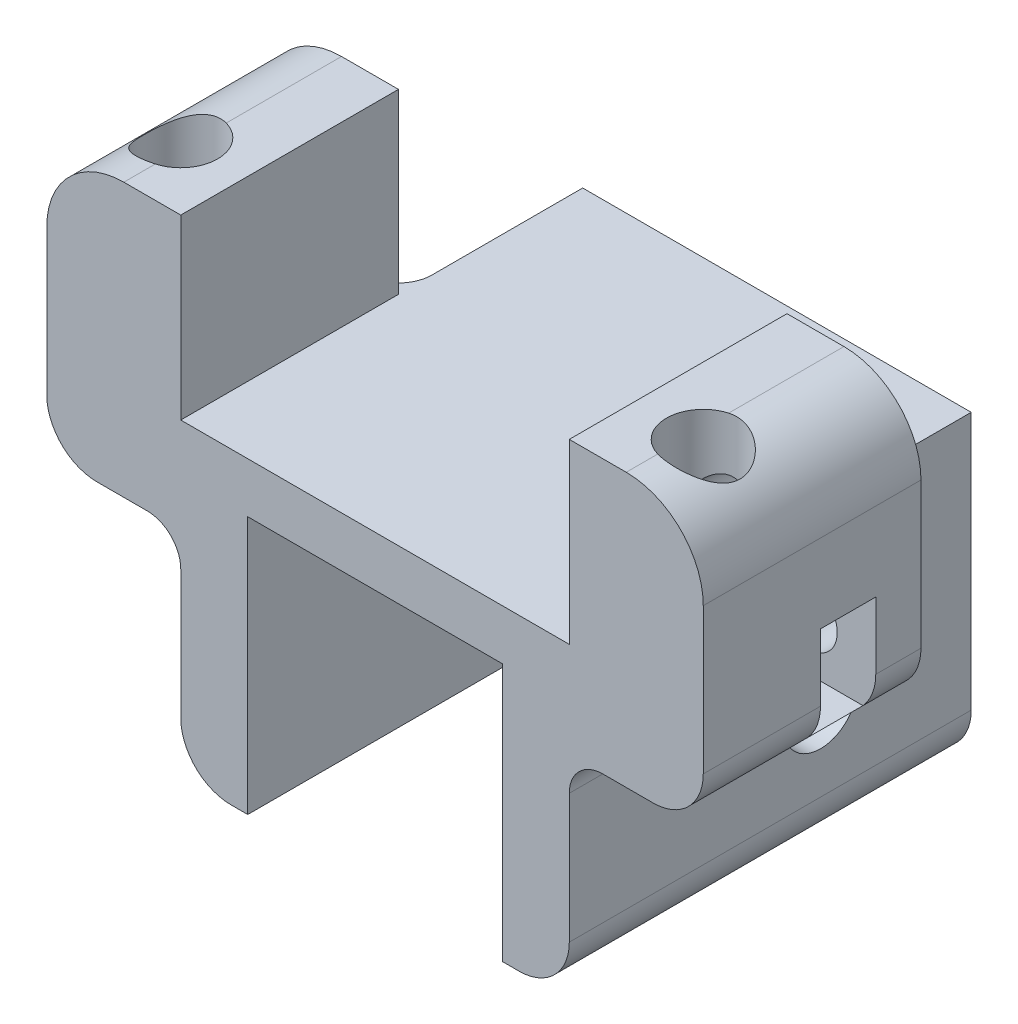
SolidWorks part; units mm, degrees
ref_plane "前视基准面" through (0, 0, 0) normal (0, 0, 1) x (1, 0, 0)
ref_plane "上视基准面" through (0, 0, 0) normal (0, 1, 0) x (1, 0, 0)
ref_plane "右视基准面" through (0, 0, 0) normal (1, 0, 0) x (0, 0, -1)
sketch "草图1" plane through (0, 0, 0) normal (0, 0, 1) x (1, 0, 0)
  line L0 (0, -1000) -> (0, 49000) construction
  line L1 (-7.6, -7.7) -> (7.6, -7.7) construction
  line L2 (-7.6, -7.7) -> (-7.6, 7.7)
  line L3 (-7.6, 7.7) -> (7.6, 7.7)
  line L4 (7.6, -7.7) -> (7.6, 7.7)
  line L5 (-7.6, -7.7) -> (7.6, 7.7) construction
  line L6 (-7.6, 7.7) -> (7.6, -7.7) construction
  line L7 (-11.6, 10.7) -> (11.6, 10.7) construction
  line L8 (-11.6, 10.7) -> (-11.6, 22.7) construction
  line L9 (-11.6, 22.7) -> (11.6, 22.7) construction
  line L10 (11.6, 10.7) -> (11.6, 22.7) construction
  line L11 (-11.6, 10.7) -> (11.6, 22.7) construction
  line L12 (-11.6, 22.7) -> (11.6, 10.7) construction
  line L13 (-7.6, -7.7) -> (-8.6, -7.7)
  line L14 (-11.6, -4.7) -> (-11.6, 3)
  line L15 (13.6, 5) -> (16.6, 5)
  line L16 (-19.6, 8) -> (-19.6, 16.7)
  line L17 (-15, 21.3) -> (-11.6, 21.3)
  line L18 (-11.6, 21.3) -> (-11.6, 10.7)
  line L19 (-11.6, 10.7) -> (11.6, 10.7)
  line L20 (11.6, 21.3) -> (11.6, 10.7)
  line L21 (15, 21.3) -> (11.6, 21.3)
  line L22 (19.6, 8) -> (19.6, 16.7)
  line L23 (-13.6, 5) -> (-16.6, 5)
  line L24 (11.6, -4.7) -> (11.6, 3)
  line L25 (7.6, -7.7) -> (8.6, -7.7)
  line L26 (-11.6, 5) -> (-11.6, 10.7)
  line L27 (11.6, 5) -> (11.6, 10.7)
  line L28 (-1000, 0) -> (49000, 0) construction
  line L29 (17.3321, 12) -> (19.6, 12)
  line L30 (19.0641, 9) -> (17.3321, 12) construction
  line L31 (17.3321, 12) -> (13.8679, 12)
  line L32 (13.8679, 12) -> (12.1359, 9)
  line L33 (12.1359, 9) -> (13.8679, 6)
  line L34 (13.8679, 6) -> (17.3321, 6)
  line L35 (17.3321, 6) -> (19.0641, 9) construction
  line L36 (17.3321, 6) -> (18.8361, 6)
  line L37 (-17.3321, 12) -> (-19.6, 12)
  line L38 (-17.3321, 12) -> (-13.8679, 12)
  line L39 (-13.8679, 12) -> (-12.1359, 9)
  line L40 (-12.1359, 9) -> (-13.8679, 6)
  line L41 (-13.8679, 6) -> (-17.3321, 6)
  line L42 (-17.3321, 6) -> (-18.8361, 6)
  line L43 (-11.6, 3) -> (-11.6, 5)
  line L44 (11.6, 3) -> (11.6, 5)
  circle A0 centre (15, 16.7) radius 1.4
  circle A1 centre (-15, 16.7) radius 1.4
  arc A2 (-15, 21.3) -> (-19.6, 16.7) centre (-15, 16.7) ccw
  arc A3 (15, 21.3) -> (19.6, 16.7) centre (15, 16.7) cw
  arc A4 (-8.6, -7.7) -> (-11.6, -4.7) centre (-8.6, -4.7) cw
  arc A5 (11.6, -4.7) -> (8.6, -7.7) centre (8.6, -4.7) cw
  arc A6 (11.6, 3) -> (13.6, 5) centre (13.6, 3) cw
  arc A7 (-11.6, 3) -> (-13.6, 5) centre (-13.6, 3) ccw
  arc A8 (16.6, 5) -> (19.6, 8) centre (16.6, 8) ccw
  arc A9 (-16.6, 5) -> (-19.6, 8) centre (-16.6, 8) cw
  circle A10 centre (-15, 16.7) radius 2 construction
  circle A11 centre (-15, 16.7) radius 2.5 construction
  circle A12 centre (-15, 16.7) radius 3 construction
  circle A13 centre (15.6, 9) radius 3 construction
  circle A14 centre (15.6, 9) radius 1.7
  circle A15 centre (-15.6, 9) radius 1.7
  point P0 (0, 0)
  point P6 (0, 16.7)
  point P18 (0, 10.7)
  point P32 (-11.6, -7.7)
  point P35 (11.6, -7.7)
  dimension "D5" = 2.8
  dimension "D9" = 3
  dimension "D10" = 5
  dimension "D11" = 8
  dimension "D12" = 4
  dimension "D13" = 5
  dimension "D14" = 6
  dimension "D16" = 2
  dimension "D17" = 3
  dimension "D18" = 6
  dimension "D20" = 3.4
  dimension "D1" = 15.2
  dimension "D2" = 15.4
  dimension "D3" = 23.2
  dimension "D4" = 12
  dimension "D6" = 30
  dimension "D7" = 3
  dimension "D8" = 4
  dimension "D15" = 39.2
  dimension "D19" = 1
  dimension "D21" = 4
extrude "凸台-拉伸1" add sketch "草图1" along normal blind 4 contours A9 L42 L41 L40 L39 L38 L37 L16 | L17 A2 L16 L37 L38 L39 L26 L18 A1 | A9 L23 A7 L43 L26 L40 L41 L42 | A5 L24 L44 L27 L19 L26 L43 L14 A4 L13 L2 L3 L4 L25 | L15 A8 L36 L34 L33 L27 L44 A6 | A3 L21 L20 L27 L32 L31 L29 L22 A0 | L36 A8 L22 L29 L31 L32 L33 L34 | A0 | A1 | A14 | A15 region at (-8.1, -7.4039, 0) region at (-15.0408, 14.5831, 0) region at (15.0408, 14.5831, 0) region at (-19.3131, 6.9637, 0) region at (18.0841, 6.0958, 0) region at (15, 16.7, 0) region at (-15, 16.7, 0) region at (15.6, 9, 0) region at (-15.6, 9, 0)
extrude "凸台-拉伸2" add sketch "草图1<5>" against normal blind 11 contours A5 L24 L44 L27 L19 L26 L43 L14 A4 L13 L2 L3 L4 L25 region at (-8.1, -7.4039, 0)
sketch "草图1<5>" plane through (0, 0, 0) normal (0, 0, 1) x (1, 0, 0) same geometry as "草图1"
extrude "凸台-拉伸3" add sketch "草图1<6>" along normal blind 9 from offset 4 contours L22 A3 L21 L20 L27 A0 | A5 L24 L27 L19 L26 L14 A4 L13 L2 L3 L4 L25 | L26 L18 L17 A2 L16 A1 | L36 A8 L22 L29 L31 L32 L33 L34 | A9 L42 L41 L40 L39 L38 L37 L16 | A9 L23 A7 L43 L26 L40 L41 L42 | L15 A8 L36 L34 L33 L27 L44 A6 | A0 | A1 | A14 | A15 region at (-8.1, -7.4039, 0) region at (-15.0408, 14.5831, 0) region at (15.0408, 14.5831, 0) region at (-19.3131, 6.9637, 0) region at (18.0841, 6.0958, 0) region at (15, 16.7, 0) region at (-15, 16.7, 0) region at (15.6, 9, 0) region at (-15.6, 9, 0)
sketch "草图1<6>" plane through (0, 0, 0) normal (0, 0, 1) x (1, 0, 0) same geometry as "草图1"
sketch "草图3" plane through (0, 0, 0) normal (1, 0, 0) x (0, 0, -1)
  circle A0 centre (2, 0) radius 2.2
  circle A1 centre (2, 0) radius 4 construction
  dimension "D1" = 4.4
  dimension "D2" = 8
  dimension "D3" = 2
extrude "切除-拉伸1" cut sketch "草图3" against normal through all and the other way through all
sketch "草图4" plane through (0, 0, 0) normal (0, 1, 0) x (1, 0, 0)
  line L0 (0, 0) -> (0, -5.5648) construction
  circle A0 centre (15.6, -9) radius 2.2
  circle A1 centre (-15.6, -9) radius 2.2
  dimension "D1" = 4.4
  dimension "D2" = 4
  dimension "D3" = 4
  dimension "D4" = 9
extrude "切除-拉伸2" cut sketch "草图4" along normal through all
extrude "切除-拉伸3" cut sketch "草图1<7>" along normal up to next contours A0 | A1 | A14 | A15 region at (15, 16.7, 0) region at (-15, 16.7, 0) region at (15.6, 9, 0) region at (-15.6, 9, 0)
sketch "草图1<7>" plane through (0, 0, 0) normal (0, 0, 1) x (1, 0, 0) same geometry as "草图1"
extrude "切除-拉伸4" cut sketch "草图1<9>" along normal blind 3.3 from offset 2.7 contours L36 A8 L22 L29 L31 L32 L33 L34 | A9 L42 L41 L40 L39 L38 L37 L16 region at (-19.3131, 6.9637, 0) region at (18.0841, 6.0958, 0)
sketch "草图1<9>" plane through (0, 0, 0) normal (0, 0, 1) x (1, 0, 0) same geometry as "草图1"
fillet "圆角1" radius 2 2 edges
